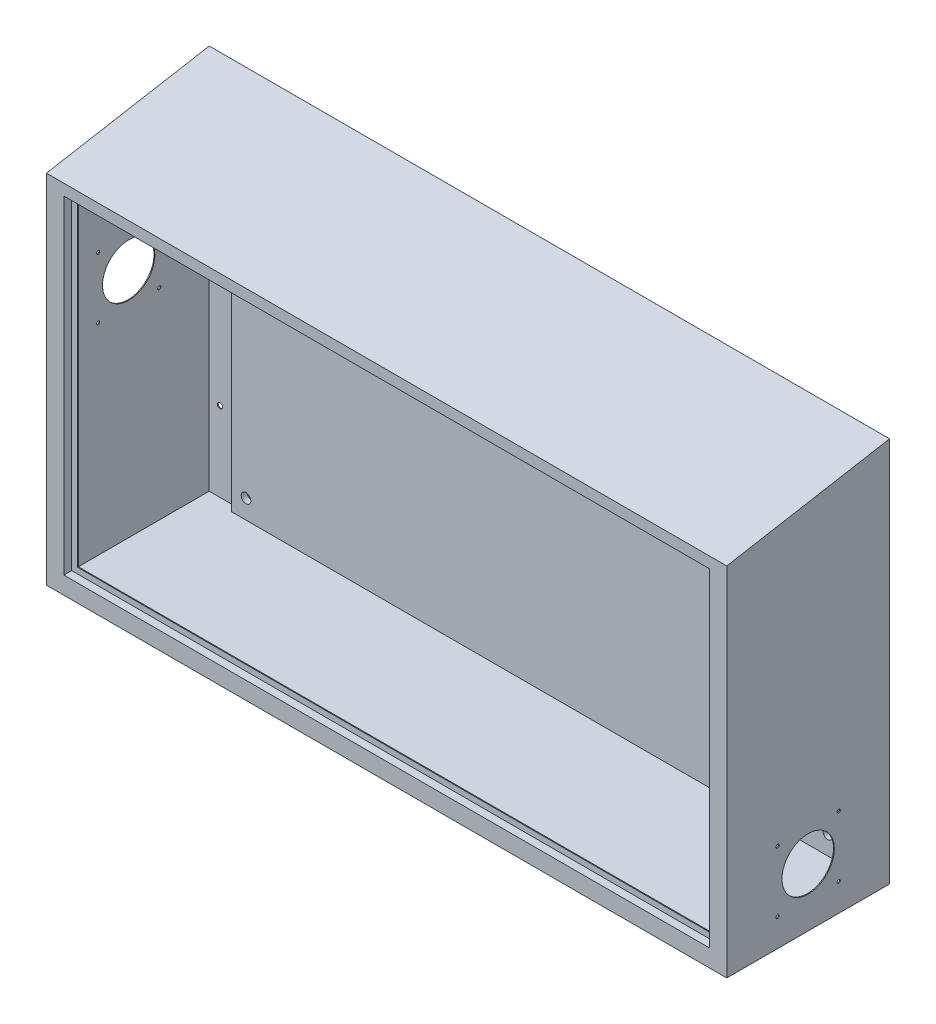
SolidWorks part; units mm, degrees
ref_plane "前视基准面" through (0, 0, 0) normal (0, 0, 1) x (1, 0, 0)
ref_plane "上视基准面" through (0, 0, 0) normal (0, 1, 0) x (1, 0, 0)
ref_plane "右视基准面" through (0, 0, 0) normal (1, 0, 0) x (0, 0, -1)
sketch "草图1" plane through (0, 0, 0) normal (0, 0, 1) x (1, 0, 0)
  line L0 (-585, -331.5) -> (-585, 331.5)
  line L1 (-585, -331.5) -> (585, -331.5)
  line L2 (-585, 331.5) -> (585, 331.5)
  line L3 (585, -331.5) -> (585, 331.5)
  line L4 (-585, -331.5) -> (585, 331.5) construction
  line L5 (-585, 331.5) -> (585, -331.5) construction
  point P1 (0, 0)
  dimension "D1" = 663
  dimension "D2" = 1170
extrude "凸台-拉伸1" add sketch "草图1" along normal blind 280
ref_plane "基准面1" through (0, 321.5041, 56.6898) normal (0, 0.9848, 0.1736) x (-1, 0, 0)
split "分割1" trim tools "基准面1" bodies to split 106 resulting bodies 109
sketch "草图2" plane through (0, 0, 280) normal (0, 0, 1) x (1, 0, 0)
  line L8 (585, 263.1284) -> (-585, 263.1284)
  line L9 (-555, 282.1284) -> (-555, -301.5)
  line L10 (-555, -301.5) -> (555, -301.5)
  line L11 (555, -301.5) -> (555, 282.1284)
  line L12 (-555, 263.1284) -> (-555, -301.5)
  line L13 (-555, -301.5) -> (555, -301.5)
  line L14 (555, -301.5) -> (555, 263.1284)
  line L15 (555, 263.1284) -> (-555, 263.1284)
  dimension "D1" = 30
  dimension "D2" = 19
extrude "切除-拉伸1" cut sketch "草图2" against normal blind 13.5
sketch "草图4" plane through (0, 0, 266.5) normal (0, 0, 1) x (1, 0, 0)
  line L9 (545, 253.1284) -> (-545, 253.1284)
  line L10 (-545, 253.1284) -> (-545, -291.5)
  line L11 (-545, -291.5) -> (545, -291.5)
  line L12 (545, -291.5) -> (545, 253.1284)
  line L13 (545, 253.1284) -> (-545, 253.1284)
  line L14 (-545, 253.1284) -> (-545, -291.5)
  line L15 (-545, -291.5) -> (545, -291.5)
  line L16 (545, -291.5) -> (545, 253.1284)
  dimension "D1" = 10
extrude "切除-拉伸2" cut sketch "草图4" against normal blind 1.5
shell "抽壳1" thickness 1.5
sketch "草图5" plane through (0, 0, 0) normal (0, 0, -1) x (-1, 0, 0)
  line L0 (0, 331.5) -> (0, -418.9502) construction
  line L1 (-585, 331.5) -> (585, 331.5) construction
  line L2 (511.5, -196.5) -> (511.5, -226.5)
  line L4 (541.5, -196.5) -> (541.5, -226.5)
  line L5 (526.5, 167.237) -> (526.5, 137.237)
  line L6 (496.5, 167.237) -> (496.5, 137.237)
  line L7 (-541.5, -196.5) -> (-541.5, -226.5)
  line L8 (-511.5, -196.5) -> (-511.5, -226.5)
  line L9 (-496.5, 167.237) -> (-496.5, 137.237)
  line L10 (-526.5, 167.237) -> (-526.5, 137.237)
  arc A0 (-541.5, -226.5) -> (-511.5, -226.5) centre (-526.5, -226.5) ccw
  arc A1 (-511.5, -196.5) -> (-541.5, -196.5) centre (-526.5, -196.5) ccw
  arc A2 (511.5, -196.5) -> (541.5, -196.5) centre (526.5, -196.5) cw
  arc A3 (541.5, -226.5) -> (511.5, -226.5) centre (526.5, -226.5) cw
  arc A4 (-526.5, 137.237) -> (-496.5, 137.237) centre (-511.5, 137.237) ccw
  arc A5 (-496.5, 167.237) -> (-526.5, 167.237) centre (-511.5, 167.237) ccw
  arc A6 (496.5, 167.237) -> (526.5, 167.237) centre (511.5, 167.237) cw
  arc A7 (526.5, 137.237) -> (496.5, 137.237) centre (511.5, 137.237) cw
  circle A8 centre (-565, 256.5) radius 4.5
  circle A9 centre (-565, -193.5) radius 4.5
  circle A10 centre (565, 256.5) radius 4.5
  circle A11 centre (565, -193.5) radius 4.5
  dimension "D3" = 9
extrude "切除-拉伸3" cut sketch "草图5" against normal up to next
sketch "草图6" plane through (585, 0, 0) normal (1, 0, 0) x (0, 0, -1)
  line L0 (-140, -331.5) -> (-140, 171.7619) construction
  line L1 (-280, -331.5) -> (0, -331.5) construction
  line L4 (-280, -231.5) -> (0, -231.5)
  line L5 (-280, -231.5) -> (0, -231.5) construction
  circle A0 centre (-140, -231.5) radius 45
  circle A1 centre (-87.5, -179) radius 2.75
  circle A2 centre (-192.5, -179) radius 2.75
  circle A3 centre (-192.5, -284) radius 2.75
  circle A4 centre (-87.5, -284) radius 2.75
  dimension "D2" = 90
  dimension "D5" = 5.5
  dimension "D1" = 100
extrude "切除-拉伸4" cut sketch "草图6" against normal up to next
sketch "草图8" plane through (-585, 0, 0) normal (-1, 0, 0) x (0, 0, 1)
  line L4 (280, 282.1284) -> (0, 331.5)
  line L5 (0, 331.5) -> (0, -331.5)
  line L6 (0, -331.5) -> (280, -331.5)
  line L7 (280, -331.5) -> (280, 282.1284)
  line L8 (280, 282.1284) -> (0, 331.5)
  line L9 (0, 331.5) -> (0, -331.5)
  line L10 (0, -331.5) -> (280, -331.5)
  line L11 (280, -331.5) -> (280, 282.1284)
  circle A0 centre (140, 68.5) radius 45
  circle A11 centre (192.5, 16) radius 2.75
  circle A12 centre (87.5, 16) radius 2.75
  circle A13 centre (87.5, 121) radius 2.75
  circle A14 centre (192.5, 121) radius 2.75
  point P2 (0, 0)
  point P5 (0, 0)
  point P6 (0, 0)
  point P7 (0, 0)
  dimension "D1" = 0
extrude "切除-拉伸6" cut sketch "草图8" against normal up to next contours A0 | A13 | A14 | A11 | A12
sketch "草图9" plane through (0, 0, 1.5) normal (0, 0, 1) x (1, 0, 0)
  line L6 (-585, -321.5) -> (585, -321.5)
  line L7 (-525, -321.5) -> (525, -321.5)
  line L8 (-525, 268.5) -> (525, 268.5)
  line L9 (-525, 263.1284) -> (-525, -301.5)
  line L10 (-525, 268.5) -> (-525, -321.5)
  line L12 (-585, 268.5) -> (585, 268.5) construction
  line L13 (525, -301.5) -> (525, 263.1284)
  line L14 (525, -321.5) -> (525, 268.5)
  line L15 (-585, -321.5) -> (585, -321.5) construction
  point P0 (0, 0)
  dimension "D1" = 10
  dimension "D2" = 30
  dimension "D3" = 590
  dimension "D4" = 30
extrude "凸台-拉伸2" add sketch "草图9" along normal blind 20
sketch "草图10" plane through (0, 0, 21.5) normal (0, 0, 1) x (1, 0, 0)
  line L1 (-525, -25.4383) -> (-146.3063, -25.4383) construction
  line L2 (-525, 130.6987) -> (-525, -181.5752) construction
  line L3 (-146.3063, -25.4383) -> (316.105, -25.4383) construction
  line L4 (0, 201.0186) -> (0, -286.8306) construction
  circle A0 centre (-500.2327, 237.877) radius 8.2869
  circle A1 centre (500.2327, 237.877) radius 8.2869
  circle A2 centre (500.2327, -288.7535) radius 8.2869
  circle A3 centre (-500.2327, -288.7535) radius 8.2869
  point P10 (500.2327, 237.877)
extrude "切除-拉伸7" cut sketch "草图10" against normal blind 10
